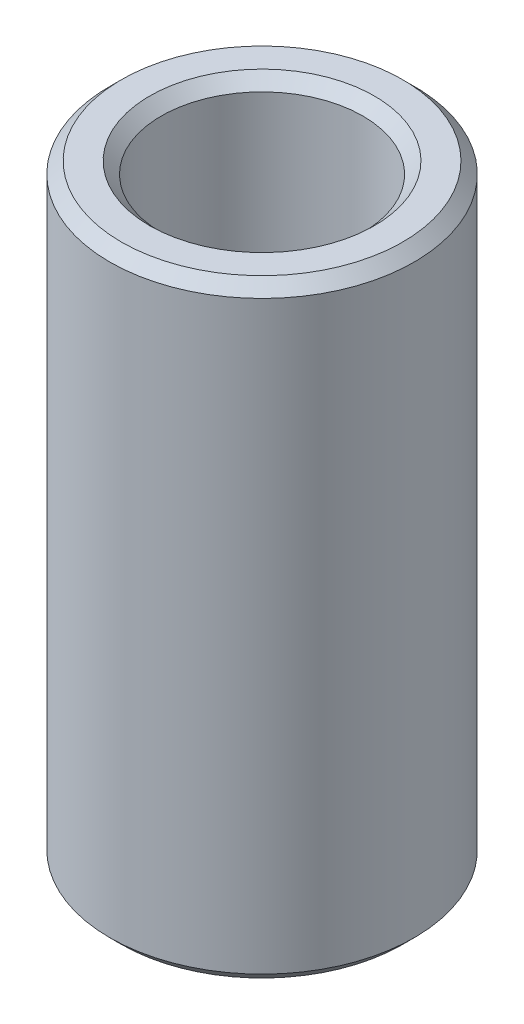
SolidWorks part; units mm, degrees
ref_plane "Front Plane" through (0, 0, 0) normal (0, 0, 1) x (1, 0, 0)
ref_plane "Top Plane" through (0, 0, 0) normal (0, 1, 0) x (1, 0, 0)
ref_plane "Right Plane" through (0, 0, 0) normal (1, 0, 0) x (0, 0, -1)
sketch "Sketch1" plane through (0, 0, 0) normal (0, 1, 0) x (1, 0, 0)
  circle A0 centre (0, 0) radius 35
  dimension "SLEEVE_OD" = 70
extrude "Boss-Extrude1" add sketch "Sketch1" along normal blind 139.8603
sketch "Sketch2" plane through (0, 0, 0) normal (0, 1, 0) x (1, 0, 0)
  circle A0 centre (0, 0) radius 23.1848
  dimension "BORE_D" = 46.3696
extrude "Cut-Extrude1" cut sketch "Sketch2" along normal through all
chamfer "Chamfer1" distance 2.656 angle 45 4 edges at (0, 139.8603, 23.1848) (0, 0, 23.1848) (0, 0, 35) (0, 139.8603, 35)
